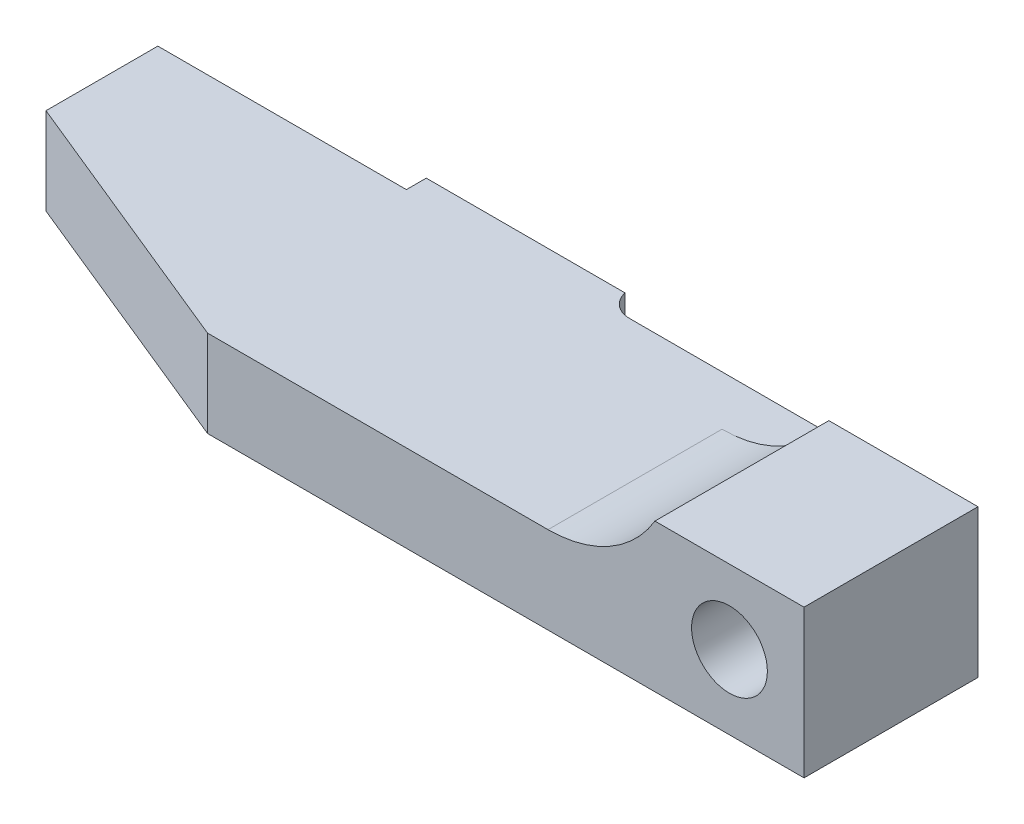
SolidWorks part; units mm, degrees
ref_plane "前视基准面" through (0, 0, 0) normal (0, 0, 1) x (1, 0, 0)
ref_plane "上视基准面" through (0, 0, 0) normal (0, 1, 0) x (1, 0, 0)
ref_plane "右视基准面" through (0, 0, 0) normal (1, 0, 0) x (0, 0, -1)
sketch "草图1" plane through (0, 0, 0) normal (0, 1, 0) x (1, 0, 0)
  line L0 (0, 0) -> (0, 9)
  line L5 (0, 0) -> (-8, 0)
  line L6 (0, 9) -> (-17, 9)
  line L8 (-24, 12) -> (-17, 12)
  line L9 (-17, 12) -> (-17, 9)
  line L10 (-8, 0) -> (-24, 0)
  line L12 (-34, 9) -> (-25, 9)
  line L14 (-24, 12) -> (-25, 12)
  line L15 (-25, 12) -> (-25, 9)
  line L16 (-34, 9) -> (-35, 9)
  line L17 (-35, 9) -> (-35, 4.5)
  line L18 (-24, 0) -> (-35, 4.5)
  point P4 (0, 0)
  dimension "D1" = 9
  dimension "D2" = 8
extrude "凸台-拉伸1" add sketch "草图1" along normal blind 3.5
sketch "草图2" plane through (0, 0, 0) normal (0, 1, 0) x (1, 0, 0)
  line L0 (0, 0) -> (-6, 0)
  line L1 (-6, 0) -> (-6, 9)
  line L2 (-6, 9) -> (0, 9)
  line L3 (0, 9) -> (0, 0)
extrude "凸台-拉伸2" add sketch "草图2" along normal blind 5.95
sketch "草图3" plane through (0, 0, 0) normal (0, 0, 1) x (1, 0, 0)
  line L0 (-6, 3.5) -> (-6, 0) construction
  line L1 (-24, 0) -> (0, 0) construction
  line L2 (-6, 0) -> (0, 0) construction
  line L3 (0, 2.975) -> (-3, 2.975) construction
  line L6 (0, 0) -> (0, 5.95)
  line L7 (0, 5.95) -> (-6, 5.95)
  line L8 (-6, 5.95) -> (-6, 3.5)
  line L9 (-6, 3.5) -> (-24, 3.5)
  line L10 (-24, 3.5) -> (-24, 0)
  line L11 (-24, 0) -> (0, 0)
  line L12 (0, 0) -> (0, 5.95) construction
  line L13 (0, 5.95) -> (-6, 5.95) construction
  line L14 (-6, 5.95) -> (-6, 3.5) construction
  circle A1 centre (-3, 2.975) radius 1.525
  dimension "D1" = 0
extrude "切除-拉伸1" cut sketch "草图3" against normal through all
sketch "草图4" plane through (0, 0, 0) normal (0, 1, 0) x (1, 0, 0)
  line L2 (-25, 9.8) -> (-17, 9.8)
  line L9 (-24, 0) -> (-6, 0)
  line L10 (-6, 0) -> (-6, 9)
  line L11 (-6, 9) -> (-17, 9)
  line L12 (-17, 9) -> (-17, 12)
  line L13 (-17, 12) -> (-25, 12)
  line L14 (-25, 12) -> (-25, 9)
  line L15 (-25, 9) -> (-35, 9)
  line L16 (-35, 9) -> (-35, 4.5)
  line L17 (-35, 4.5) -> (-24, 0)
  line L21 (-17, 9.8) -> (-17, 12)
  line L22 (-17, 12) -> (-25, 12)
  line L23 (-25, 12) -> (-25, 9.8)
  dimension "D1" = 0
extrude "切除-拉伸2" cut sketch "草图4" along normal blind 10
sketch "草图5" plane through (0, 0, 0) normal (0, 0, 1) x (1, 0, 0)
  line L0 (-6, 5.95) -> (-6, 0)
  line L5 (-17, 0) -> (0, 0)
  line L6 (-17, 3.5) -> (-17, 0)
  line L7 (-6, 3.5) -> (-17, 3.5)
  line L8 (0, 5.95) -> (-6, 5.95)
  line L9 (0, 0) -> (0, 5.95)
  line L10 (-6, 0) -> (0, 0)
  line L13 (0, 5.95) -> (-6, 5.95)
  line L14 (0, 0) -> (0, 5.95)
  line L17 (-6, 5.95) -> (-6, 3.5)
  line L18 (-6, 5.95) -> (-6, 3.5)
  dimension "D1" = 0
extrude "切除-拉伸4" cut sketch "草图5" along normal blind 2 from offset 9 contours L0 L10 L14 L13 offset against normal yes
fillet "圆角1" radius 5 1 edges at (-6, 3.5, -3.5)
fillet "圆角2" radius 1 2 edges at (-6, 1.75, -9) (-6, 3.5, -8)
fillet "圆角3" radius 1 1 edges at (-17, 1.75, -9)
